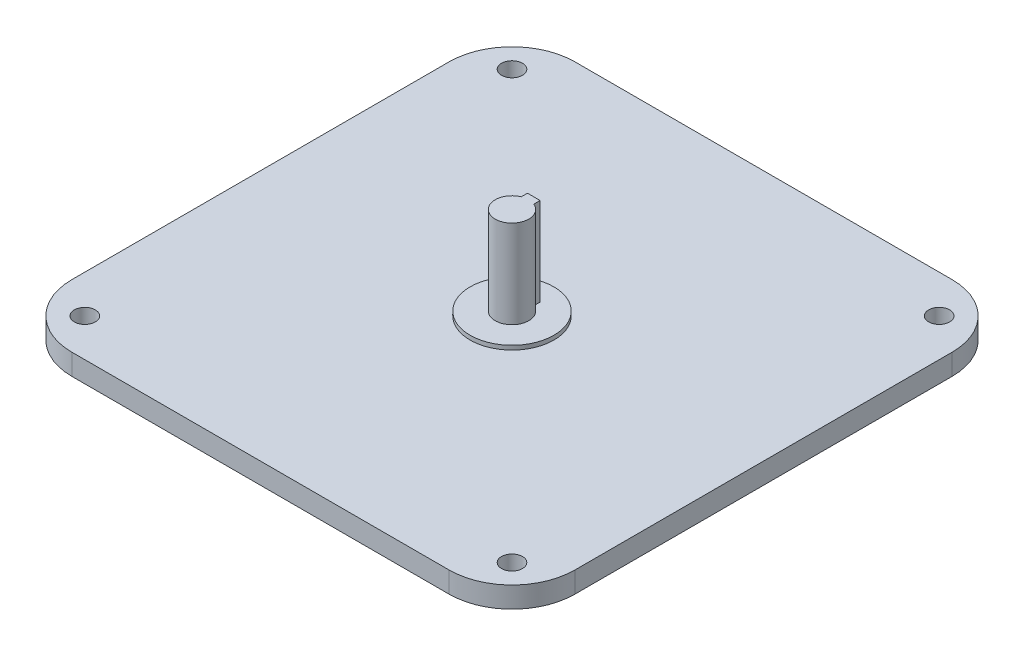
SolidWorks part; units mm, degrees
ref_plane "Plano frontal" through (0, 0, 0) normal (0, 0, 1) x (1, 0, 0)
ref_plane "Plano superior" through (0, 0, 0) normal (0, 1, 0) x (1, 0, 0)
ref_plane "Plano direito" through (0, 0, 0) normal (1, 0, 0) x (0, 0, -1)
sketch "Esboço1" plane through (0, 0, 0) normal (0, 1, 0) x (1, 0, 0)
  line L1 (-60, -60) -> (60, -60)
  line L2 (-60, -60) -> (-60, 60)
  line L3 (-60, 60) -> (60, 60)
  line L4 (60, -60) -> (60, 60)
  line L5 (-60, -60) -> (60, 60) construction
  line L6 (-60, 60) -> (60, -60) construction
  circle A4 centre (-50.9554, -50.9554) radius 2.5
  circle A5 centre (-50.9554, -50.9554) radius 2.5 construction
  circle A6 centre (-50.9554, 50.9554) radius 2.5
  circle A7 centre (50.9554, 50.9554) radius 2.5
  circle A8 centre (50.9554, -50.9554) radius 2.5
  point P0 (0, 0)
  point P16 (0, -2.0854)
  point P19 (0, 0)
  dimension "D3" = 4
  dimension "D1" = 120
  dimension "D2" = 120
extrude "Ressalto-extrusão1" add sketch "Esboço1" along normal mid plane 5
fillet "Filete1" radius 15 4 edges at (-60, 0, -60) (60, 0, -60) (60, 0, 60) (-60, 0, 60)
sketch "Esboço2" plane through (0, 2.5, 0) normal (0, 1, 0) x (1, 0, 0)
  line L0 (-1.5, 3.7081) -> (-1.5, 2.2) construction
  line L1 (-1.5, 5.2) -> (1.5, 5.2)
  line L2 (-1.5, 5.2) -> (-1.5, 3.7081)
  line L3 (-1.5, 2.2) -> (1.5, 2.2) construction
  line L4 (1.5, 5.2) -> (1.5, 3.7081)
  line L5 (0, 3.7) -> (1.5, 2.2) construction
  line L6 (-1.5, 2.2) -> (0, 3.7) construction
  line L7 (-1.5, 2.2) -> (1.5, 2.2) construction
  line L8 (1.5, 2.2) -> (1.5, 3.7081) construction
  arc A1 (-1.5, 3.7081) -> (1.5, 3.7081) centre (0, 0) ccw
  point P3 (0, 3.7)
  dimension "D1" = 4
  dimension "D2" = 3
  dimension "D3" = 3
  dimension "D4" = 2.2
extrude "Ressalto-extrusão2" add sketch "Esboço2" along normal blind 22
sketch "Esboço3" plane through (0, 2.5, 0) normal (0, 1, 0) x (1, 0, 0)
  circle A0 centre (0, 0) radius 10
  dimension "D1" = 20
extrude "Ressalto-extrusão3" add sketch "Esboço3" along normal blind 1
move or copy body "Corpo-Converter em corpo de malha1" [suppressed] bodies to move or copy 103 copy no translate (0, 0, 0) parameters "D1"=0, "D2"=0, "D3"=0
